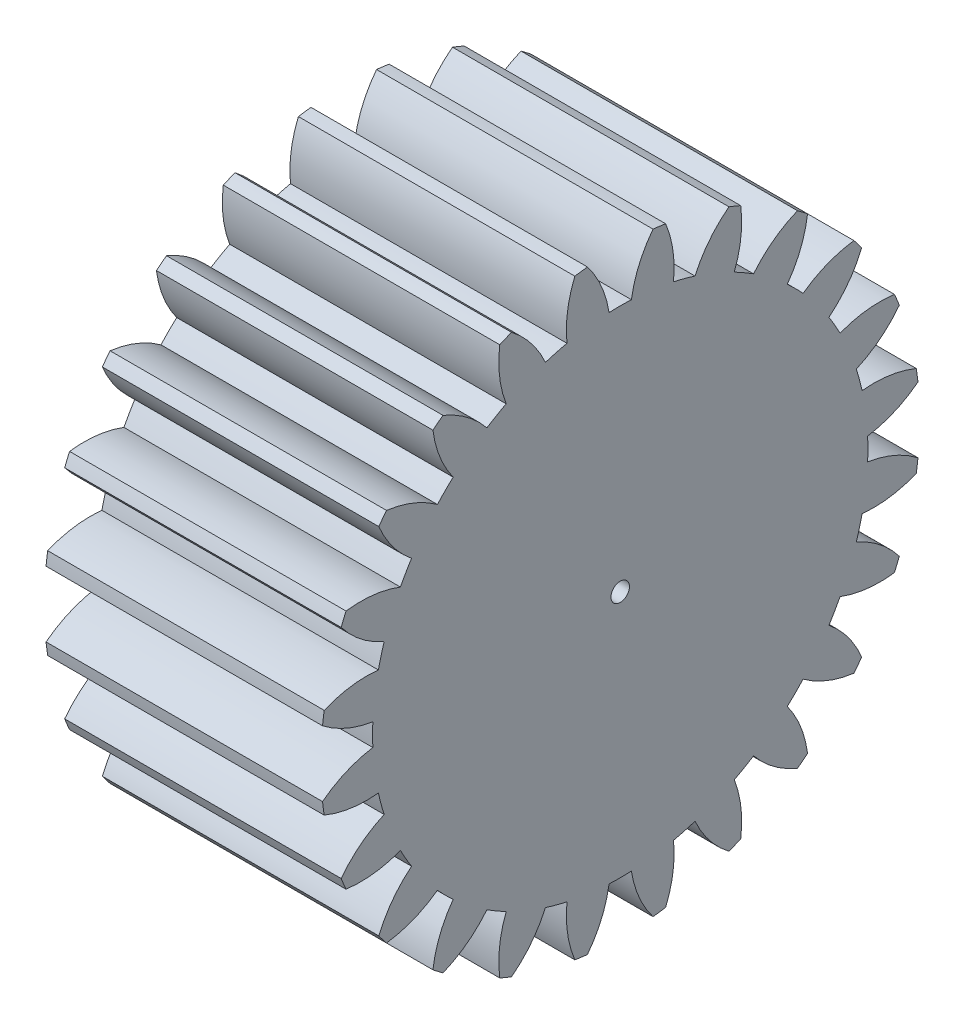
SolidWorks part; units mm, degrees
ref_plane "Plane1" through (0, 0, 0) normal (0, 0, 1) x (1, 0, 0)
ref_plane "Plane2" through (0, 0, 0) normal (0, 1, 0) x (1, 0, 0)
ref_plane "Plane3" through (0, 0, 0) normal (1, 0, 0) x (0, 0, -1)
sketch "HoldingSke" plane through (0, 0, 0) normal (0, 1, 0) x (1, 0, 0)
  line L0 (0, 0) -> (589.383, -262.4102)
  line L1 (-15, 0) -> (100, 0) construction
  line L2 (0, 0) -> (-2.1039, 2.3779)
  line L3 (0, 0) -> (-11.863, 4.5341)
  line L4 (0, 0) -> (7.8894, 3.5126)
  line L5 (0, 0) -> (-46.8476, -17.4728)
  line L6 (0, 0) -> (-9.9476, -6.7116)
  line L7 (-2.1039, 2.3779) -> (8.6589, 51.2071)
  line L8 (-76.2, 54.61) -> (-76.1, 54.61)
  line L9 (-71.009, 38.7566) -> (-53.1078, 45.2721)
  line L10 (-76.2, 71.12) -> (104.1128, 71.12)
  line L11 (0, 0) -> (-12, 0)
  line L12 (-76.2, 101.6) -> (-76.162, 101.6)
  line L13 (24.9733, 27.94) -> (52.9518, 28.4284)
  line L14 (24.9733, 27.94) -> (24.9743, 27.94)
  line L15 (24.9733, 27.94) -> (100.4006, 29.5858)
  line L16 (-63.627, -1) -> (-12.827, -1)
  circle A0 centre (0, 0) radius 0.4
  circle A1 centre (0, 0) radius 10.749
  circle A2 centre (0, 0) radius 37.5
  circle A3 centre (0, 0) radius 0.4
  dimension "Num_teeth" = 24
  dimension "Pitch_radius" = 180.3128
  dimension "Width" = 12
  dimension "Thickness" = 12
sketch "BasProSke" plane through (0, 0, 0) normal (0, 1, 0) x (1, 0, 0)
  line L0 (-10, 0) -> (60, 0) construction
  line L1 (0, 0) -> (0, 13)
  line L2 (0, 0) -> (12, 0)
  line L3 (12, 0) -> (12, 13)
  line L4 (12, 13) -> (0, 13)
  dimension "Thickness" = 12
  dimension "Diameter" = 26
revolve "Base-Revolve" add sketch "BasProSke" angle 360 about L0
sketch "TooCutSke" plane through (0, 0, 0) normal (1, 0, 0) x (0, 0, -1)
  line L1 (0, 0) -> (0, 107) construction
  line L2 (0, 0) -> (-0.8513, 11.9698) construction
  line L3 (0, 0) -> (-3.127, 23.752) construction
  line L4 (-0.8513, 11.9698) -> (-1.5635, 11.876) construction
  arc A0 (0.4834, 10.7381) -> (-0.4834, 10.7381) centre (0, 0) ccw
  arc A1 (1.9532, 13.5046) -> (-1.9532, 13.5046) centre (0, 0) ccw
  circle A2 centre (0, 0) radius 12 construction
  circle A3 centre (0, 0) radius 11.2763 construction
  arc A4 (-0.4834, 10.7381) -> (-1.9532, 13.5046) centre (-5.2252, 9.9926) ccw
  arc A5 (1.9532, 13.5046) -> (0.4834, 10.7381) centre (5.2252, 9.9926) ccw
extrude "ToothCut" cut sketch "TooCutSke" along normal through all
fillet "Breaks" [suppressed] radius 0.02 tangent propagation no
fillet "RootFillets" [suppressed] radius 0.251
pattern_circular "TeethCuts" count 24 every 15 about axis through (-10, 0, 0) along (1, 0, 0) of "ToothCut", "RootFillets", "Breaks"
sketch "HubNeaOneSke" plane through (0, 0, 0) normal (-1, 0, 0) x (0, 0, 1)
  circle A0 centre (0, 0) radius 10.749
  dimension "Diameter" = 21.498
extrude "HubNearOne" [suppressed] add sketch "HubNeaOneSke" along normal blind 38.0013
sketch "HubNeaBotSke" plane through (0, 0, 0) normal (-1, 0, 0) x (0, 0, 1)
  circle A0 centre (0, 0) radius 10.749
  dimension "Diameter" = 21.498
extrude "HubNearBoth" [suppressed] add sketch "HubNeaBotSke" along normal blind 19.0006
ref_plane "FarPln" through (12, 0, 0) normal (1, 0, 0) x (0, 0, -1)
sketch "HubFarSke" plane through (12, 0, 0) normal (1, 0, 0) x (0, 0, -1)
  circle A0 centre (0, 0) radius 10.749
  dimension "Diameter" = 21.498
extrude "HubFar" [suppressed] add sketch "HubFarSke" along normal blind 19.0006
sketch "BorSke" plane through (0, 0, 0) normal (1, 0, 0) x (0, 0, -1)
  circle A0 centre (0, 0) radius 0.4
  dimension "Diameter" = 0.8
extrude "Bore" cut sketch "BorSke" along normal mid plane 100.0026
sketch "KeySke" plane through (0, 0, 0) normal (1, 0, 0) x (0, 0, -1)
  line L0 (-0.05, 0) -> (-0.05, 0.5)
  line L1 (-0.05, 0.5) -> (0.05, 0.5)
  line L2 (0.05, 0.5) -> (0.05, 0)
  line L3 (0, 0) -> (0, 34) construction
  line L4 (-0.05, 0) -> (0.05, 0)
  dimension "Width" = 0.1
extrude "Keyway" [suppressed] cut sketch "KeySke" along normal mid plane 100.0026
pattern_circular "Keyway2" [suppressed] count 2 every 90 about axis through (-10, 0, 0) along (1, 0, 0) reverse direction yes
scale "Scale1" scale about centroid uniform scaling yes scale factor 2
sketch "Sketch1" plane through (18, 0, 0) normal (1, 0, 0) x (0, 0, -1)
  circle A0 centre (0, 0) radius 23.749 construction
  dimension "D1" = 47.498
equation "' \"Module@HoldingSke\" = 6.35"
equation "' \"Num_teeth@HoldingSke\" = 12"
equation "' \"Ap@HoldingSke\" =  20"
equation "' \"Ap@HoldingSke\" = 20"
equation "' \"Width@HoldingSke\" = 0.5 * 25.4"
equation "' \"Hub_dia@HoldingSke\"= 1 * 25.4"
equation "' \"Hub_dia@HoldingSke\" = 1 * 25.4"
equation "' \"Overall_len@HoldingSke\" = 1.0 * 25.4"
equation "' \"Bore@HoldingSke\" = 0.75 * 25.4"
equation "' \"T_dim@HoldingSke\" = 0.1 * 25.4"
equation "' \"Width@KeySke\" = 0.25 * 25.4"
equation "' \"Show_teeth@HoldingSke\" = 13"
equation "' \"Backlash@HoldingSke\" = 0.009 * 25.4"
equation "' \"Addendum_fac@HoldingSke\" = 1.0"
equation "' \"Dedendum_fac@HoldingSke\" = 1.25"
equation "' \"Dedendum_add@HoldingSke\" = 0.00005 * 25.4"
equation "' \"Clearance_fac@HoldingSke\" = 0.25"
equation "\"Pitch@HoldingSke\" = 1 / \"Module@HoldingSke\""
equation "\"Overcut_dia@TooCutSke\" = (\"Num_teeth@HoldingSke\" + 2 * \"Addendum_fac@HoldingSke\") / \"Pitch@HoldingSke\" + 0.002 * 25.4"
equation "\"Pitch_dia@TooCutSke\" = \"Num_teeth@HoldingSke\" / \"Pitch@HoldingSke\""
equation "\"Base_dia@TooCutSke\" = \"Num_teeth@HoldingSke\" / \"Pitch@HoldingSke\" * cos((\"Ap@HoldingSke\"  * 3.14159265 / 180))"
equation "\"Root_dia@TooCutSke\" = (\"Num_teeth@HoldingSke\" + 2) / \"Pitch@HoldingSke\" - 2 * (\"Addendum_fac@HoldingSke\" + \"Dedendum_fac@HoldingSke\") / \"Pitch@HoldingSke\" - \"Dedendum_add@HoldingSke\" * 2"
equation "\"Half_ang@TooCutSke\" = 180 / \"Num_teeth@HoldingSke\""
equation "\"Half_CT@TooCutSke\" = \"Num_teeth@HoldingSke\" / \"Pitch@HoldingSke\" * sin((3.14159265 / 2 / \"Num_teeth@HoldingSke\")) / 2 - 7 * \"Backlash@HoldingSke\" / 4"
equation "\"Flank_rad@TooCutSke\" = \"Num_teeth@HoldingSke\" / \"Pitch@HoldingSke\" / 5"
equation "\"Radius@RootFillets\" = \"Clearance_fac@HoldingSke\" / \"Pitch@HoldingSke\" + \"Dedendum_add@HoldingSke\""
equation "\"Break_rad@Breaks\" = 0.02 / \"Pitch@HoldingSke\""
equation "\"Thickness@HoldingSke\" = \"Width@HoldingSke\""
equation "\"OAL@HoldingSke\" = \"Thickness@HoldingSke\""
equation "\"MHD@HoldingSke\" = (\"Num_teeth@HoldingSke\" + 2) / \"Pitch@HoldingSke\" - 2 * (\"Addendum_fac@HoldingSke\" + \"Dedendum_fac@HoldingSke\")  / \"Pitch@HoldingSke\" - \"Dedendum_add@HoldingSke\" * 2"
equation "\"MBD@HoldingSke\" = (\"Num_teeth@HoldingSke\" + 2) / \"Pitch@HoldingSke\" - 2 * (\"Addendum_fac@HoldingSke\" + \"Dedendum_fac@HoldingSke\")  / \"Pitch@HoldingSke\" - \"Dedendum_add@HoldingSke\" * 2 - 0.002 * 25.4"
equation "\"MHD@HoldingSke\" = ((sgn( \"MHD@HoldingSke\" - \"Hub_dia@HoldingSke\" )-1)*( \"MHD@HoldingSke\" - \"Hub_dia@HoldingSke\" ))/-2+ \"Hub_dia@HoldingSke\""
equation "\"MBD@HoldingSke\" = ((sgn( \"MBD@HoldingSke\" - \"Bore@HoldingSke\" )-1)*( \"MBD@HoldingSke\" - \"Bore@HoldingSke\" ))/-2+ \"Bore@HoldingSke\""
equation "\"OAL@HoldingSke\" = ((sgn( \"OAL@HoldingSke\" - \"Overall_len@HoldingSke\" )+1)*( \"OAL@HoldingSke\" - \"Overall_len@HoldingSke\" ))/2 + \"Overall_len@HoldingSke\" + 0.000002 * 25.4"
equation "\"Num_teeth@TeethCuts\" = int( \"Show_teeth@HoldingSke\" ) + 1"
equation "\"Num_teeth@TeethCuts\" = ((sgn( \"Num_teeth@TeethCuts\" - \"Num_teeth@HoldingSke\" )-1)*( \"Num_teeth@TeethCuts\" - \"Num_teeth@HoldingSke\" ))/-2+ \"Num_teeth@HoldingSke\""
equation "\"Num_teeth@TeethCuts\" = ((sgn( \"Num_teeth@TeethCuts\" - 2.0)+1)*( \"Num_teeth@TeethCuts\" - 2.0))/2 +2.0"
equation "\"Angle@TeethCuts\" = 360.0 / \"Num_teeth@HoldingSke\""
equation "\"Diameter@BasProSke\" = (\"Num_teeth@HoldingSke\" + 2 * \"Addendum_fac@HoldingSke\") / \"Pitch@HoldingSke\""
equation "\"Thickness@BasProSke\"  = \"Thickness@HoldingSke\""
equation "' \"Fillet_rad@BasProSke\" =  \"Thickness@HoldingSke\" * 0.05"
equation "' \"Fillet_rad@BasProSke\" = \"Thickness@HoldingSke\" * 0.05"
equation "\"MHD@HoldingSke\" = ((sgn( \"MHD@HoldingSke\" - \"Root_dia@TooCutSke\" )-1)*( \"MHD@HoldingSke\" - \"Root_dia@TooCutSke\" ))/-2+ \"Root_dia@TooCutSke\""
equation "\"Diameter@HubNeaOneSke\" = \"MHD@HoldingSke\""
equation "\"Length@HubNearOne\" = \"OAL@HoldingSke\" - \"Thickness@BasProSke\""
equation "\"Diameter@HubNeaBotSke\" = \"MHD@HoldingSke\""
equation "\"Length@HubNearBoth\" = ( \"OAL@HoldingSke\" - \"Thickness@BasProSke\" ) / 2.0"
equation "\"Thickness@FarPln\" = \"Thickness@BasProSke\""
equation "\"Diameter@HubFarSke\" = \"MHD@HoldingSke\""
equation "\"Length@HubFar\" = ( \"OAL@HoldingSke\" - \"Thickness@BasProSke\" ) / 2.0"
equation "\"Diameter@BorSke\" = \"MBD@HoldingSke\""
equation "\"D1@Bore\" = \"OAL@HoldingSke\" * 2.0"
equation "\"D1@Keyway\" = \"OAL@HoldingSke\" * 2.0"
equation "\"Offset@KeySke\" = \"T_dim@HoldingSke\" + \"MBD@HoldingSke\" / 2.0"
